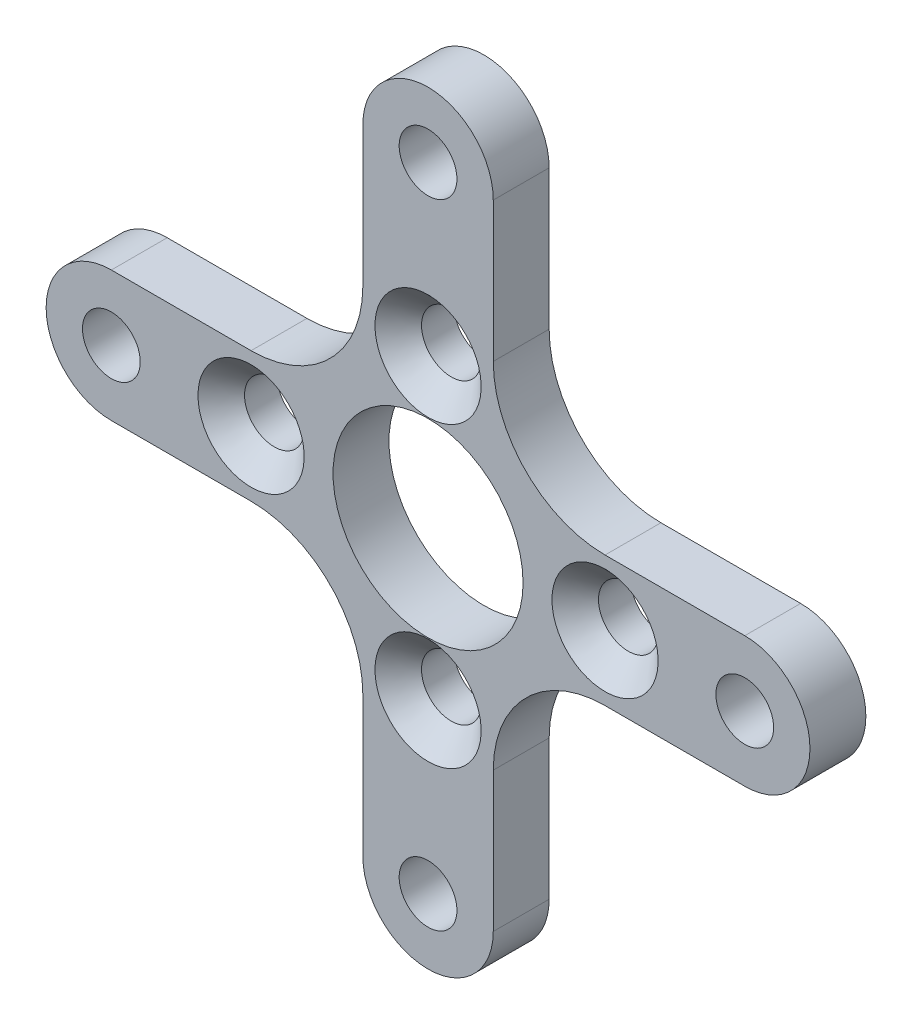
SolidWorks part; units mm, degrees
material "6061-T6 (SS)"
ref_plane "Front Plane" through (0, 0, 0) normal (1, 0, 0) x (0, 1, 0)
ref_plane "Top Plane" through (0, 0, 0) normal (0, 0, 1) x (0, 1, 0)
ref_plane "Right Plane" through (0, 0, 0) normal (0, 1, 0) x (-1, 0, 0)
sketch "Sketch1" plane through (0, 0, 0) normal (0, 0, 1) x (0, 1, 0)
  line L0 (0, 20.5) -> (0, -20.5) construction
  line L1 (-20.5, 0) -> (20.5, 0) construction
  line L2 (-8, 0) -> (8, 0) construction
  line L3 (0, 9.5) -> (0, -9.5) construction
  line L4 (-17, 0) -> (17, 0) construction
  line L5 (0, 17) -> (0, -17) construction
  line L6 (3.5, 17) -> (3.5, 9.5)
  line L7 (-3.5, 17) -> (-3.5, 9.5)
  line L8 (-17, 3.5) -> (-9.5, 3.5)
  line L9 (17, 3.5) -> (9.5, 3.5)
  line L10 (-17, -3.5) -> (-9.5, -3.5)
  line L11 (-3.5, -9.5) -> (-3.5, -17)
  line L12 (3.5, -17) -> (3.5, -9.5)
  line L13 (9.5, -3.5) -> (17, -3.5)
  circle A0 centre (0, 0) radius 5.1
  circle A1 centre (0, 9.5) radius 1.6
  circle A2 centre (8, 0) radius 1.6
  circle A3 centre (-8, 0) radius 1.6
  circle A4 centre (0, -9.5) radius 1.6
  circle A5 centre (0, 17) radius 1.55
  circle A6 centre (17, 0) radius 1.55
  circle A7 centre (-17, 0) radius 1.55
  circle A8 centre (0, -17) radius 1.55
  arc A9 (-3.5, 17) -> (3.5, 17) centre (0, 17) cw
  arc A10 (-17, -3.5) -> (-17, 3.5) centre (-17, 0) cw
  arc A11 (3.5, -17) -> (-3.5, -17) centre (0, -17) cw
  arc A12 (17, 3.5) -> (17, -3.5) centre (17, 0) cw
  arc A13 (3.5, -9.5) -> (9.5, -3.5) centre (9.5, -9.5) cw
  arc A14 (3.5, 9.5) -> (9.5, 3.5) centre (9.5, 9.5) ccw
  arc A15 (-3.5, -9.5) -> (-9.5, -3.5) centre (-9.5, -9.5) ccw
  arc A16 (-3.5, 9.5) -> (-9.5, 3.5) centre (-9.5, 9.5) cw
  point P18 (0, 0)
  point P19 (0, 0)
  point P21 (0, 0)
  point P23 (0, 0)
  point P30 (0, 20.5)
  point P40 (-20.5, 0)
  point P41 (20.5, 0)
  point P42 (0, -20.5)
  dimension "D1" = 10.2
  dimension "D2" = 3.2
  dimension "D7" = 3.1
  dimension "D8" = 7
  dimension "D9" = 6
  dimension "D3" = 19
  dimension "D4" = 16
  dimension "D5" = 34
  dimension "D6" = 34
extrude "Boss-Extrude1" add sketch "Sketch1" along normal blind 3
chamfer "Chamfer1" distance 1.25 angle 45 4 edges at (11.1, 0, 3) (1.6, 8, 3) (-7.9, 0, 3) (1.6, -8, 3)
